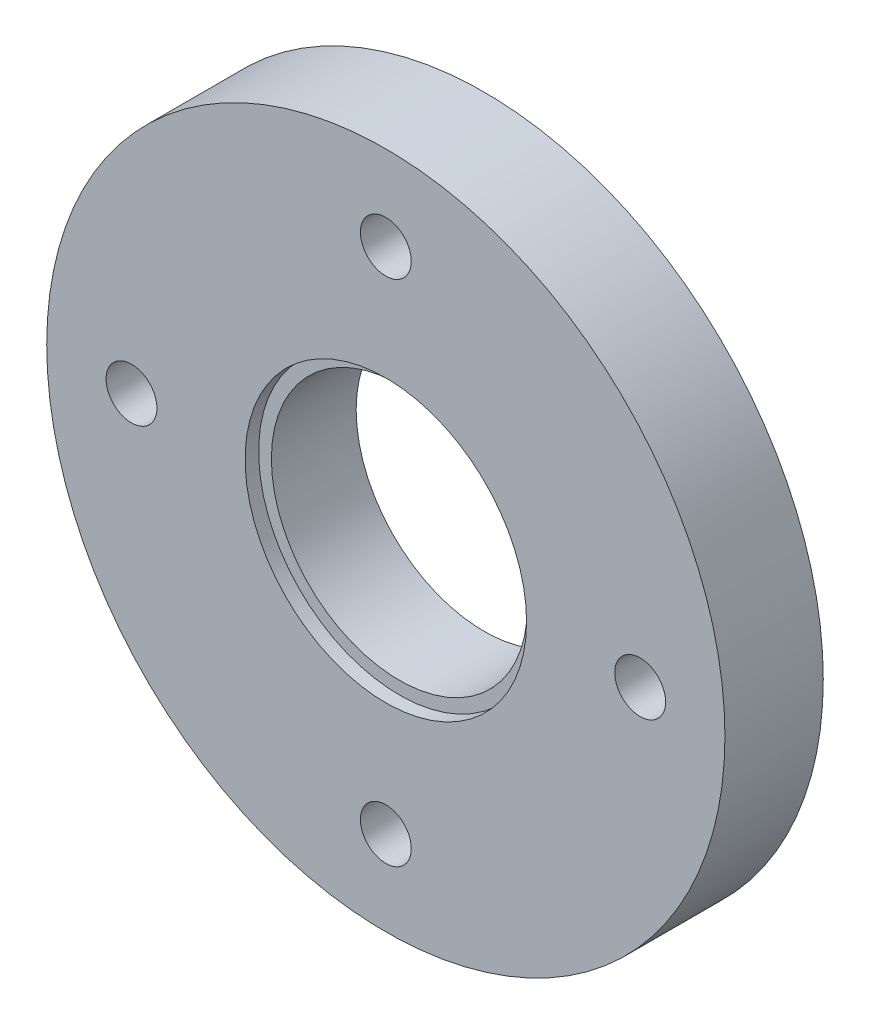
SolidWorks part; units mm, degrees
ref_plane "正面" through (0, 0, 0) normal (0, 0, 1) x (1, 0, 0)
ref_plane "平面" through (0, 0, 0) normal (0, 1, 0) x (1, 0, 0)
ref_plane "右側面" through (0, 0, 0) normal (1, 0, 0) x (0, 0, -1)
sketch "ｽｹｯﾁ1" plane through (0, 0, 0) normal (0, 0, 1) x (1, 0, 0)
  line L0 (-15, 0) -> (0, 0) construction
  line L1 (0, 0) -> (0, 15) construction
  circle A0 centre (0, 0) radius 20
  circle A1 centre (0, 0) radius 7.55
  circle A2 centre (0, 15) radius 1.5
  circle A3 centre (15, 0) radius 1.5
  circle A4 centre (0, -15) radius 1.5
  circle A5 centre (-15, 0) radius 1.5
  point P7 (-15.1262, 0)
  dimension "D1" = 15.1
  dimension "D2" = 40
  dimension "D3" = 3
  dimension "D4" = 15
  dimension "D5" = 4
extrude "ﾎﾞｽ - 押し出し1" add sketch "ｽｹｯﾁ1" along normal blind 5.8
sketch "ｽｹｯﾁ2" plane through (0, 0, 5.8) normal (0, 0, 1) x (1, 0, 0)
  circle A0 centre (0, 0) radius 8.3
  dimension "D1" = 16.6
extrude "ｶｯﾄ - 押し出し1" cut sketch "ｽｹｯﾁ2" against normal blind 0.8
